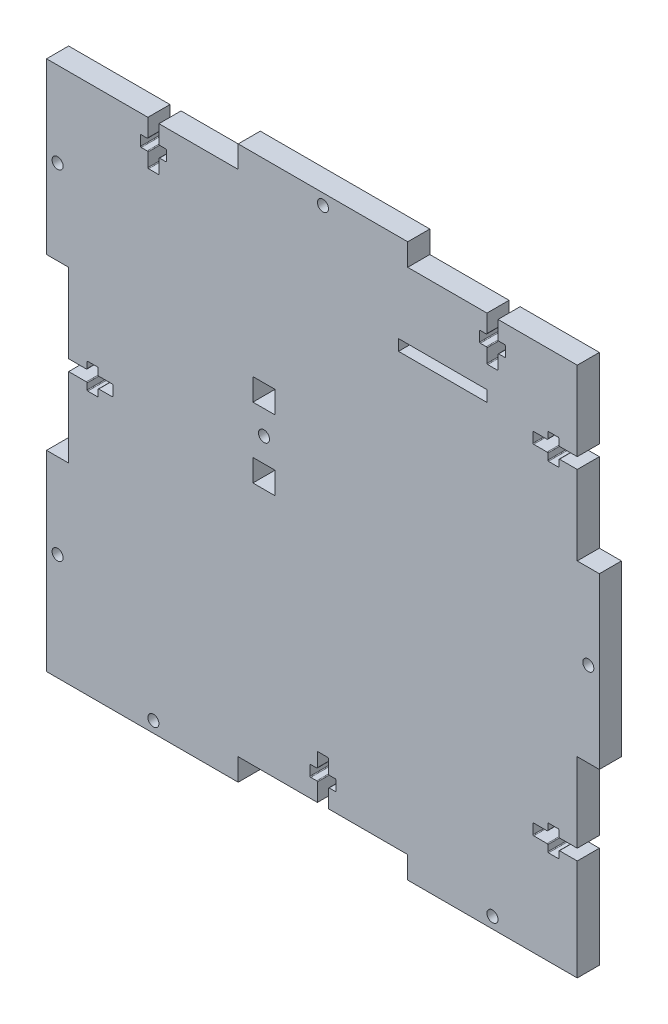
SolidWorks part; units mm, degrees
ref_plane "Front Plane" through (0, 0, 0) normal (0, 0, 1) x (1, 0, 0)
ref_plane "Top Plane" through (0, 0, 0) normal (0, 1, 0) x (1, 0, 0)
ref_plane "Right Plane" through (0, 0, 0) normal (1, 0, 0) x (0, 0, -1)
sketch "Sketch1" plane through (0, 0, 0) normal (0, 0, 1) x (1, 0, 0)
  line L0 (-69, 69) -> (-23, 69)
  line L5 (-75, -75) -> (75, -75) construction
  line L6 (-75, -75) -> (-75, 75) construction
  line L7 (-75, 75) -> (75, 75) construction
  line L8 (75, -75) -> (75, 75) construction
  line L9 (75, 23) -> (69, 23)
  line L10 (69, -23) -> (75, -23)
  line L11 (-69, -69) -> (69, -69) construction
  line L12 (-69, -69) -> (-69, 69) construction
  line L13 (-69, 69) -> (69, 69) construction
  line L14 (69, -69) -> (69, 69) construction
  line L15 (-69, -69) -> (69, 69) construction
  line L16 (69, -69) -> (69, -23)
  line L17 (-23, 69) -> (-23, 75)
  line L18 (-23, 75) -> (23, 75)
  line L19 (23, 75) -> (23, 69)
  line L20 (23, 69) -> (69, 69)
  line L21 (75, -23) -> (75, 23)
  line L22 (69, 23) -> (69, 69)
  line L23 (-75, 23) -> (-69, 23)
  line L24 (-69, 69) -> (-75, 69)
  line L25 (-75, 69) -> (-75, 23)
  line L26 (69, -69) -> (69, -75)
  line L27 (69, -75) -> (23, -75)
  line L28 (23, -75) -> (23, -69)
  line L29 (23, -69) -> (-23, -69)
  line L30 (-23, -69) -> (-23, -75)
  line L31 (-23, -75) -> (-69, -75)
  line L32 (-69, -75) -> (-69, -69) construction
  line L33 (-69, 23) -> (-69, -23)
  line L34 (-69, -23) -> (-75, -23)
  line L35 (-75, -23) -> (-75, -69)
  line L36 (-75, -69) -> (-69, -69) construction
  line L37 (-46, 69) -> (-46, -75) construction
  line L38 (-69, 69) -> (69, -69) construction
  line L39 (-75, -75) -> (-69, -75)
  line L40 (-75, -75) -> (-75, -69)
  point P0 (0, 0)
  point P6 (-7, -7)
  point P26 (0, -75)
  point P27 (-75, 0)
  dimension "D1" = 150
  dimension "D2" = 150
  dimension "D5" = 46
  dimension "D3" = 6
  dimension "D6" = 6
  dimension "D7" = 6
extrude "Box Side" add sketch "Sketch1" along normal blind 6
sketch "Sketch2" plane through (0, 0, 6) normal (0, 0, 1) x (1, 0, 0)
  line L0 (23, 72) -> (-23, 72) construction
  line L1 (23, 75) -> (23, 69) construction
  line L2 (-23, 69) -> (-23, 75) construction
  line L3 (-46, 69) -> (-46, -75) construction
  line L5 (0, 75) -> (0, 69) construction
  line L6 (-23, 75) -> (23, 75) construction
  line L7 (-69, 69) -> (69, 69) construction
  line L16 (-46, 69) -> (-46, -75) construction
  line L21 (0, -69) -> (0, 69) construction
  line L35 (-69, 69) -> (-23, 69) construction
  line L36 (-44.5, 69) -> (-44.5, 64.2)
  line L37 (-44.3, 64) -> (-42.7, 64)
  line L38 (-42.5, 63.8) -> (-42.5, 61.2)
  line L39 (-42.7, 61) -> (-44.3, 61)
  line L40 (-44.5, 60.8) -> (-44.5, 57.2)
  line L46 (-44.7, 57) -> (-47.3, 57)
  line L48 (-44.5, 69) -> (-47.5, 69)
  line L51 (-47.5, 60.8) -> (-47.5, 57.2)
  line L52 (-49.3, 61) -> (-47.7, 61)
  line L53 (-49.5, 63.8) -> (-49.5, 61.2)
  line L54 (-47.7, 64) -> (-49.3, 64)
  line L55 (-47.5, 69) -> (-47.5, 64.2)
  line L56 (47.5, 69) -> (47.5, 64.2)
  line L57 (47.7, 64) -> (49.3, 64)
  line L58 (49.5, 63.8) -> (49.5, 61.2)
  line L59 (49.3, 61) -> (47.7, 61)
  line L60 (47.5, 60.8) -> (47.5, 57.2)
  line L61 (44.5, 69) -> (47.5, 69)
  line L62 (44.7, 57) -> (47.3, 57)
  line L63 (44.5, 60.8) -> (44.5, 57.2)
  line L64 (42.7, 61) -> (44.3, 61)
  line L65 (42.5, 63.8) -> (42.5, 61.2)
  line L66 (44.3, 64) -> (42.7, 64)
  line L67 (44.5, 69) -> (44.5, 64.2)
  line L68 (-69, -69) -> (69, 69) construction
  line L69 (-69, -69) -> (69, 69) construction
  line L70 (75, 0) -> (69, 0) construction
  line L71 (72, 23) -> (72, -23) construction
  line L72 (69, 44.5) -> (64.2, 44.5)
  line L73 (64, 44.3) -> (64, 42.7)
  line L74 (63.8, 42.5) -> (61.2, 42.5)
  line L75 (61, 42.7) -> (61, 44.3)
  line L76 (60.8, 44.5) -> (57.2, 44.5)
  line L77 (57, 44.7) -> (57, 47.3)
  line L78 (69, 44.5) -> (69, 47.5)
  line L79 (60.8, 47.5) -> (57.2, 47.5)
  line L80 (61, 49.3) -> (61, 47.7)
  line L81 (63.8, 49.5) -> (61.2, 49.5)
  line L82 (64, 47.7) -> (64, 49.3)
  line L83 (69, 47.5) -> (64.2, 47.5)
  line L84 (69, -47.5) -> (64.2, -47.5)
  line L85 (64, -47.7) -> (64, -49.3)
  line L86 (63.8, -49.5) -> (61.2, -49.5)
  line L87 (61, -49.3) -> (61, -47.7)
  line L88 (60.8, -47.5) -> (57.2, -47.5)
  line L89 (69, -44.5) -> (69, -47.5)
  line L90 (57, -44.7) -> (57, -47.3)
  line L91 (60.8, -44.5) -> (57.2, -44.5)
  line L92 (61, -42.7) -> (61, -44.3)
  line L93 (63.8, -42.5) -> (61.2, -42.5)
  line L94 (64, -44.3) -> (64, -42.7)
  line L95 (69, -44.5) -> (64.2, -44.5)
  line L120 (-69, 69) -> (69, -69) construction
  line L121 (-69, 69) -> (69, -69) construction
  line L122 (-1.5, -69) -> (1.5, -69)
  line L123 (-23, -69) -> (23, -69) construction
  line L124 (1.5, -69) -> (1.5, -64.2)
  line L125 (1.7, -64) -> (3.3, -64)
  line L126 (3.5, -63.8) -> (3.5, -61.2)
  line L127 (3.3, -61) -> (1.7, -61)
  line L128 (1.5, -60.8) -> (1.5, -57.2)
  line L129 (1.3, -57) -> (-1.3, -57)
  line L130 (-1.5, -60.8) -> (-1.5, -57.2)
  line L131 (-3.3, -61) -> (-1.7, -61)
  line L132 (-3.5, -63.8) -> (-3.5, -61.2)
  line L133 (-1.7, -64) -> (-3.3, -64)
  line L134 (-1.5, -69) -> (-1.5, -64.2)
  line L135 (-69, -1.5) -> (-64.2, -1.5)
  line L136 (-64, -1.7) -> (-64, -3.3)
  line L137 (-63.8, -3.5) -> (-61.2, -3.5)
  line L138 (-61, -3.3) -> (-61, -1.7)
  line L139 (-60.8, -1.5) -> (-57.2, -1.5)
  line L140 (-57, 1.3) -> (-57, -1.3)
  line L141 (-60.8, 1.5) -> (-57.2, 1.5)
  line L142 (-61, 3.3) -> (-61, 1.7)
  line L143 (-63.8, 3.5) -> (-61.2, 3.5)
  line L144 (-64, 1.7) -> (-64, 3.3)
  line L145 (-69, 1.5) -> (-64.2, 1.5)
  line L146 (-69, -1.5) -> (-69, 1.5)
  line L147 (-69, -72) -> (-23, -72) construction
  line L148 (-23, 69) -> (-75, 69) construction
  line L149 (-23, -75) -> (-23, -69) construction
  line L150 (-69, -69) -> (-69, -75) construction
  line L151 (-75, -75) -> (-23, -75) construction
  circle A0 centre (0, 72) radius 1.5
  arc A1 (-44.5, 57.2) -> (-44.7, 57) centre (-44.7, 57.2) cw
  arc A2 (-44.3, 61) -> (-44.5, 60.8) centre (-44.3, 60.8) ccw
  arc A3 (-42.5, 61.2) -> (-42.7, 61) centre (-42.7, 61.2) cw
  arc A4 (-42.7, 64) -> (-42.5, 63.8) centre (-42.7, 63.8) cw
  arc A5 (-44.5, 64.2) -> (-44.3, 64) centre (-44.3, 64.2) ccw
  arc A6 (-47.5, 64.2) -> (-47.7, 64) centre (-47.7, 64.2) cw
  arc A7 (-49.3, 64) -> (-49.5, 63.8) centre (-49.3, 63.8) ccw
  arc A8 (-49.5, 61.2) -> (-49.3, 61) centre (-49.3, 61.2) ccw
  arc A9 (-47.7, 61) -> (-47.5, 60.8) centre (-47.7, 60.8) cw
  arc A10 (-47.5, 57.2) -> (-47.3, 57) centre (-47.3, 57.2) ccw
  arc A11 (47.5, 57.2) -> (47.3, 57) centre (47.3, 57.2) cw
  arc A12 (47.7, 61) -> (47.5, 60.8) centre (47.7, 60.8) ccw
  arc A13 (49.5, 61.2) -> (49.3, 61) centre (49.3, 61.2) cw
  arc A14 (49.3, 64) -> (49.5, 63.8) centre (49.3, 63.8) cw
  arc A15 (47.5, 64.2) -> (47.7, 64) centre (47.7, 64.2) ccw
  arc A16 (44.5, 64.2) -> (44.3, 64) centre (44.3, 64.2) cw
  arc A17 (42.7, 64) -> (42.5, 63.8) centre (42.7, 63.8) ccw
  arc A18 (42.5, 61.2) -> (42.7, 61) centre (42.7, 61.2) ccw
  arc A19 (44.3, 61) -> (44.5, 60.8) centre (44.3, 60.8) cw
  arc A20 (44.5, 57.2) -> (44.7, 57) centre (44.7, 57.2) ccw
  arc A21 (57.2, 44.5) -> (57, 44.7) centre (57.2, 44.7) cw
  arc A22 (61, 44.3) -> (60.8, 44.5) centre (60.8, 44.3) ccw
  arc A23 (61.2, 42.5) -> (61, 42.7) centre (61.2, 42.7) cw
  arc A24 (64, 42.7) -> (63.8, 42.5) centre (63.8, 42.7) cw
  arc A25 (64.2, 44.5) -> (64, 44.3) centre (64.2, 44.3) ccw
  arc A26 (64.2, 47.5) -> (64, 47.7) centre (64.2, 47.7) cw
  arc A27 (64, 49.3) -> (63.8, 49.5) centre (63.8, 49.3) ccw
  arc A28 (61.2, 49.5) -> (61, 49.3) centre (61.2, 49.3) ccw
  arc A29 (61, 47.7) -> (60.8, 47.5) centre (60.8, 47.7) cw
  arc A30 (57.2, 47.5) -> (57, 47.3) centre (57.2, 47.3) ccw
  arc A31 (57.2, -47.5) -> (57, -47.3) centre (57.2, -47.3) cw
  arc A32 (61, -47.7) -> (60.8, -47.5) centre (60.8, -47.7) ccw
  arc A33 (61.2, -49.5) -> (61, -49.3) centre (61.2, -49.3) cw
  arc A34 (64, -49.3) -> (63.8, -49.5) centre (63.8, -49.3) cw
  arc A35 (64.2, -47.5) -> (64, -47.7) centre (64.2, -47.7) ccw
  arc A36 (64.2, -44.5) -> (64, -44.3) centre (64.2, -44.3) cw
  arc A37 (64, -42.7) -> (63.8, -42.5) centre (63.8, -42.7) ccw
  arc A38 (61.2, -42.5) -> (61, -42.7) centre (61.2, -42.7) ccw
  arc A39 (61, -44.3) -> (60.8, -44.5) centre (60.8, -44.3) cw
  arc A40 (57.2, -44.5) -> (57, -44.7) centre (57.2, -44.7) ccw
  circle A41 centre (72, 0) radius 1.5
  arc A62 (1.5, -57.2) -> (1.3, -57) centre (1.3, -57.2) ccw
  arc A63 (1.7, -61) -> (1.5, -60.8) centre (1.7, -60.8) cw
  arc A64 (3.5, -61.2) -> (3.3, -61) centre (3.3, -61.2) ccw
  arc A65 (3.3, -64) -> (3.5, -63.8) centre (3.3, -63.8) ccw
  arc A66 (1.5, -64.2) -> (1.7, -64) centre (1.7, -64.2) cw
  arc A67 (-1.5, -64.2) -> (-1.7, -64) centre (-1.7, -64.2) ccw
  arc A68 (-3.3, -64) -> (-3.5, -63.8) centre (-3.3, -63.8) cw
  arc A69 (-3.5, -61.2) -> (-3.3, -61) centre (-3.3, -61.2) cw
  arc A70 (-1.7, -61) -> (-1.5, -60.8) centre (-1.7, -60.8) ccw
  arc A71 (-1.5, -57.2) -> (-1.3, -57) centre (-1.3, -57.2) cw
  arc A72 (-57.2, -1.5) -> (-57, -1.3) centre (-57.2, -1.3) ccw
  arc A73 (-61, -1.7) -> (-60.8, -1.5) centre (-60.8, -1.7) cw
  arc A74 (-61.2, -3.5) -> (-61, -3.3) centre (-61.2, -3.3) ccw
  arc A75 (-64, -3.3) -> (-63.8, -3.5) centre (-63.8, -3.3) ccw
  arc A76 (-64.2, -1.5) -> (-64, -1.7) centre (-64.2, -1.7) cw
  arc A77 (-64.2, 1.5) -> (-64, 1.7) centre (-64.2, 1.7) ccw
  arc A78 (-64, 3.3) -> (-63.8, 3.5) centre (-63.8, 3.3) cw
  arc A79 (-61.2, 3.5) -> (-61, 3.3) centre (-61.2, 3.3) cw
  arc A80 (-61, 1.7) -> (-60.8, 1.5) centre (-60.8, 1.7) ccw
  arc A81 (-57.2, 1.5) -> (-57, 1.3) centre (-57.2, 1.3) cw
  circle A82 centre (-46, -72) radius 1.5
  circle A83 centre (46, -72) radius 1.5
  circle A84 centre (-72, 46) radius 1.5
  circle A85 centre (-72, -46) radius 1.5
  point P6 (0, 72)
  point P38 (0, 0)
  point P56 (-46, 57)
  point P88 (46, 57)
  point P161 (57, 46)
  point P162 (57, -46)
  point P198 (0, -57)
  point P231 (-57, 0)
  point P234 (-42.5, 62.5)
  dimension "D1" = 3
  dimension "D2" = 0.2
  dimension "D8" = 0.2
  dimension "D14" = 3
  dimension "D4" = 3
  dimension "D7" = 1.5
  dimension "D10" = 3
  dimension "D12" = 1.5
  dimension "D9" = 12
  dimension "D11" = 5
  dimension "D13" = 7
  dimension "D3" = 12
  dimension "D5" = 7
  dimension "D6" = 5
extrude "Screw Cut-outs" cut sketch "Sketch2" against normal through all
sketch "Sketch3" plane through (0, 0, 6) normal (0, 0, 1) x (1, 0, 0)
  line L0 (69, 23) -> (69, 44.5) construction
  line L1 (44.5, 51) -> (20.5, 51)
  line L2 (44.5, 51) -> (44.5, 48)
  line L3 (44.5, 48) -> (20.5, 48)
  line L4 (20.5, 51) -> (20.5, 48)
  line L5 (44.5, 69) -> (23, 69) construction
  line L6 (75, -23) -> (75, 23) construction
  line L7 (-13, 22.32) -> (-19, 22.32)
  line L8 (-13, 22.32) -> (-13, 16.32)
  line L9 (-13, 16.32) -> (-19, 16.32)
  line L10 (-19, 22.32) -> (-19, 16.32)
  line L11 (-13, 3.32) -> (-19, 3.32)
  line L12 (-13, 3.32) -> (-13, -2.68)
  line L13 (-13, -2.68) -> (-19, -2.68)
  line L14 (-19, 3.32) -> (-19, -2.68)
  line L15 (-23, -69) -> (-1.5, -69) construction
  line L16 (-16, 3.32) -> (-16, 16.32) construction
  circle A0 centre (-16, 9.82) radius 1.5
  point P22 (-16, 16.32)
  point P27 (-16, 9.82)
  dimension "D9" = 3
  dimension "D1" = 3
  dimension "D2" = 24.5
  dimension "D3" = 24
  dimension "D4" = 18
  dimension "D5" = 6
  dimension "D6" = 88
  dimension "D7" = 66.32
  dimension "D8" = 13
extrude "Grooves" cut sketch "Sketch3" against normal through all
equation "\"filletRadius\"=0.2"
equation "\"D8@Sketch2\"=\"filletRadius\""
equation "\"D2@Sketch2\"=\"filletRadius\""
equation "\"fingerWidth\"= 46"
equation "\"D5@Sketch1\"=\"fingerWidth\""
equation "\"wallThickness\"= 6"
equation "\"D3@Sketch1\" = \"wallThickness\""
equation "\"D6@Sketch1\" = \"wallThickness\""
equation "\"D7@Sketch1\" = \"wallThickness\""
equation "\"D1@Box Side\" = \"wallThickness\""
equation "\"M3\"= 3"
equation "\"D14@Sketch2\"=\"M3\""
equation "\"D1@Sketch2\"=\"M3\""
equation "\"D12@Sketch2\"=\"M3\"/2"
equation "\"nutThickness\"=3"
equation "\"D10@Sketch2\" = \"nutThickness\""
equation "\"boltLength\"= 12"
equation "\"D9@Sketch2\" = \"boltLength\""
equation "\"distanceToNut\"= 5"
equation "\"D11@Sketch2\" = \"distanceToNut\""
equation "\"D13@Sketch2\" = \"nutWidth\""
equation "\"D7@Sketch2\"=\"M3\"/2"
equation "\"D4@Sketch2\" = \"nutThickness\""
equation "\"D3@Sketch2\" = \"boltLength\""
equation "\"D5@Sketch2\" = \"nutWidth\""
equation "\"D6@Sketch2\" = \"distanceToNut\""
equation "\"sideLength\"=150"
equation "\"D1@Sketch1\"=\"sideLength\""
equation "\"D2@Sketch1\"=\"sideLength\""
equation "\"nutWidth\"=7"
